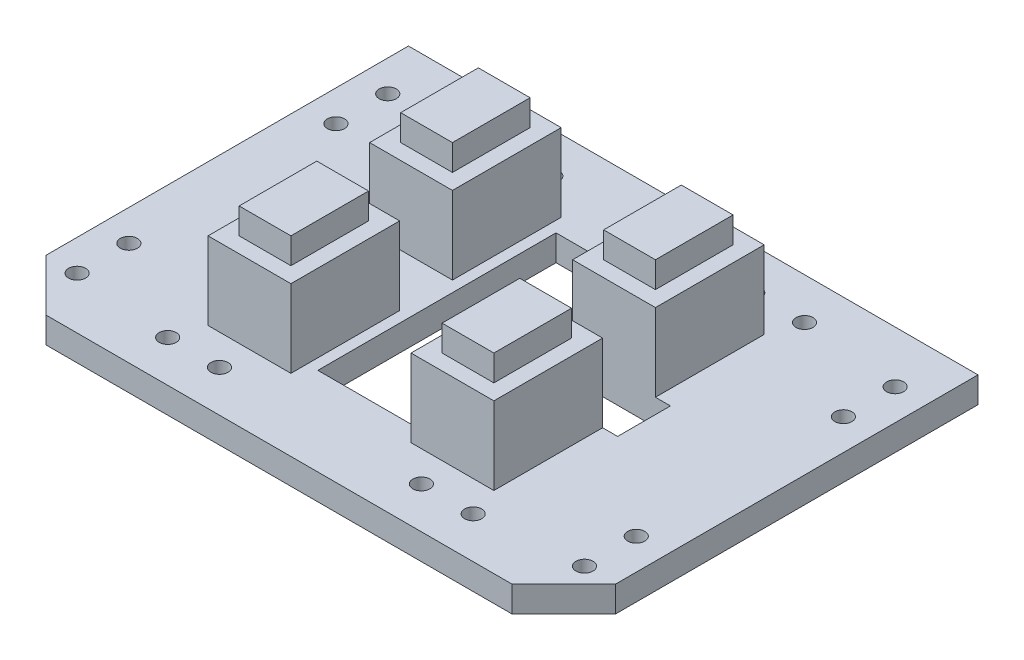
SolidWorks part; units mm, degrees
material "PLA+ esun"
ref_plane "Front Plane" through (0, 0, 0) normal (0, 0, 1) x (1, 0, 0)
ref_plane "Top Plane" through (0, 0, 0) normal (0, 1, 0) x (1, 0, 0)
ref_plane "Right Plane" through (0, 0, 0) normal (1, 0, 0) x (0, 0, -1)
sketch "Sketch1" plane through (0, 0, 0) normal (0, 1, 0) x (1, 0, 0)
  line L0 (0, 0) -> (49.8029, 0) construction
  line L1 (-77.5, 77.5) -> (77.5, 77.5)
  line L2 (-77.5, 77.5) -> (-77.5, -77.5)
  line L3 (-77.5, -77.5) -> (77.5, -77.5)
  line L4 (77.5, 77.5) -> (77.5, -77.5)
  line L5 (-77.5, 77.5) -> (77.5, -77.5) construction
  line L6 (-77.5, -77.5) -> (77.5, 77.5) construction
  line L7 (-9.5, 23) -> (9.5, 23)
  line L8 (-9.5, 23) -> (-9.5, -23)
  line L9 (-9.5, -23) -> (9.5, -23)
  line L10 (9.5, 23) -> (9.5, -23)
  line L11 (-9.5, 23) -> (9.5, -23) construction
  line L12 (-9.5, -23) -> (9.5, 23) construction
  line L14 (0, 0) -> (0, 35.7746) construction
  line L17 (-77.5, -77.5) -> (-42.5, -77.5)
  line L18 (-77.5, -77.5) -> (-77.5, -24.25)
  line L19 (-77.5, -24.25) -> (-42.5, -24.25)
  line L20 (-42.5, -77.5) -> (-42.5, -24.25)
  line L21 (-77.5, 24.25) -> (-42.5, 24.25)
  line L22 (-42.5, 77.5) -> (-42.5, 24.25)
  line L23 (42.5, -77.5) -> (42.5, -24.25)
  line L24 (77.5, -24.25) -> (42.5, -24.25)
  line L25 (42.5, 77.5) -> (42.5, 24.25)
  line L26 (77.5, 24.25) -> (42.5, 24.25)
  line L27 (20, -40) -> (42.5, -40)
  line L28 (-42.5, 24.25) -> (-77.5, 24.25)
  line L29 (-42.5, 24.25) -> (-42.5, -24.25)
  line L30 (-42.5, -24.25) -> (-77.5, -24.25)
  line L31 (-77.5, 24.25) -> (-77.5, -24.25)
  line L32 (42.5, 24.25) -> (77.5, 24.25)
  line L33 (42.5, 24.25) -> (42.5, -24.25)
  line L34 (42.5, -24.25) -> (77.5, -24.25)
  line L35 (77.5, 24.25) -> (77.5, -24.25)
  line L36 (-42.5, 77.5) -> (42.5, 77.5)
  line L37 (-42.5, 77.5) -> (-42.5, 40)
  line L38 (-42.5, 40) -> (42.5, 40)
  line L39 (42.5, 77.5) -> (42.5, 40)
  line L40 (-42.5, -77.5) -> (42.5, -77.5)
  line L41 (-42.5, -77.5) -> (-42.5, -40)
  line L42 (-42.5, -40) -> (-20, -40)
  line L43 (42.5, -77.5) -> (42.5, -40)
  line L45 (-20, -40) -> (-20, -77.5)
  line L46 (-20, -77.5) -> (20, -77.5)
  line L47 (20, -40) -> (20, -77.5)
  line L49 (-20, -77.5) -> (20, -77.5)
  line L50 (-20, -77.5) -> (-20, -40)
  line L51 (-20, -40) -> (20, -40)
  line L52 (20, -77.5) -> (20, -40)
  circle A1 centre (29.5, 32) radius 1.65
  circle A2 centre (19.5, 32) radius 1.65
  circle A3 centre (19.5, -32) radius 1.65
  circle A4 centre (29.5, -32) radius 1.65
  circle A5 centre (-29.5, -32) radius 1.65
  circle A6 centre (-19.5, -32) radius 1.65
  circle A7 centre (-19.5, 32) radius 1.65
  circle A8 centre (-29.5, 32) radius 1.65
  point P0 (0, 0)
  point P6 (0, 0)
  point P13 (0, 0)
  dimension "D5" = 9
  dimension "D8" = 20
  dimension "D9" = 53.25
  dimension "D6" = 3.3
  dimension "D1" = 155
  dimension "D2" = 155
  dimension "D3" = 46
  dimension "D4" = 19
  dimension "D7" = 2
  dimension "D10" = 35
  dimension "D11" = 37.5
  dimension "D12" = 37.5
  dimension "D13" = 22.5
  dimension "D14" = 22.5
extrude "Boss-Extrude3" add sketch "Sketch1" along normal blind 5 contours L4 L26 L25 L1 L22 L21 L2 L19 L20 L3 L23 L24 A7 A6 A5 A3 A2 A1 L7 L10 L9 L8 A4 A8 region at (0, 0, -38.8327)
sketch "Sketch6" plane through (0, 5, 0) normal (0, 1, 0) x (1, 0, 0)
  line L0 (-24.6, 8.1) -> (-14.6, 8.1)
  line L9 (-14.6, 8.1) -> (-14.6, 23.1)
  line L10 (-24.6, 8.1) -> (-24.6, 23.1)
  line L11 (-24.7, 8) -> (-14.5, 8)
  line L12 (-24.7, 23.2) -> (-14.5, 23.2)
  line L13 (-24.7, 23.2) -> (-24.7, -23.2)
  line L14 (-24.7, -23.2) -> (-14.5, -23.2)
  line L15 (-14.5, 23.2) -> (-14.5, -23.2)
  line L16 (9.5, 23) -> (-9.5, 23)
  line L17 (9.5, 23) -> (9.5, -23)
  line L18 (9.5, -23) -> (-9.5, -23)
  line L19 (-9.5, 23) -> (-9.5, -23)
  line L20 (9.5, 23) -> (-9.5, -23) construction
  line L21 (9.5, -23) -> (-9.5, 23) construction
  line L22 (-24.7, -8) -> (-14.5, -8)
  line L23 (0, 0) -> (0, -14.0514) construction
  line L24 (24.6, 23.1) -> (14.6, 23.1)
  line L29 (14.6, -8.1) -> (14.6, -23.1)
  line L30 (0, 0) -> (7.1407, 0) construction
  line L35 (-24.6, -8.1) -> (-14.6, -8.1)
  line L36 (-24.6, -8.1) -> (-24.6, -23.1)
  line L37 (-24.6, -23.1) -> (-14.6, -23.1)
  line L38 (-14.6, -8.1) -> (-14.6, -23.1)
  line L39 (-24.6, 23.1) -> (-14.6, 23.1)
  line L40 (24.6, -23.1) -> (14.6, -23.1)
  line L41 (24.6, -8.1) -> (24.6, -23.1)
  line L42 (24.6, -8.1) -> (14.6, -8.1)
  line L43 (24.7, -8) -> (14.5, -8)
  line L44 (14.5, 23.2) -> (14.5, -23.2)
  line L45 (24.7, -23.2) -> (14.5, -23.2)
  line L46 (24.7, 23.2) -> (24.7, -23.2)
  line L47 (24.7, 23.2) -> (14.5, 23.2)
  line L48 (24.7, 8) -> (14.5, 8)
  line L49 (24.6, 8.1) -> (24.6, 23.1)
  line L50 (14.6, 8.1) -> (14.6, 23.1)
  line L51 (24.6, 8.1) -> (14.6, 8.1)
  point P4 (0, 0)
  dimension "D1" = 0.2
  dimension "D2" = 5
  dimension "D3" = 0.2
  dimension "D4" = 10.2
  dimension "D5" = 15.2
  dimension "D6" = 15.2
  dimension "D7" = 0.1
  dimension "D8" = 0.1
  dimension "D9" = 0.1
  dimension "D10" = 0.1
extrude "Boss-Extrude4" add sketch "Sketch6" along normal blind 20 contours L51 L49 L24 L50 | L39 L10 L0 L9 | L38 L35 L36 L37 | L41 L42 L29 L40 region at (-19.6, 5, -15.6) region at (19.6, 5, -15.6) region at (19.6, 5, 15.6) region at (-19.6, 5, 15.6)
sketch "Sketch8" plane through (0, 5, 0) normal (0, 1, 0) x (1, 0, 0)
  line L0 (0, 0) -> (0, -16.476) construction
  line L1 (-27.6, 26.1) -> (-11.6, 26.1)
  line L2 (-27.6, 26.1) -> (-27.6, -26.1)
  line L3 (-27.6, -26.1) -> (-11.6, -26.1)
  line L4 (-11.6, 26.1) -> (-11.6, -26.1)
  line L5 (-24.6, 23.1) -> (-14.6, 23.1) construction
  line L6 (-24.6, 8.1) -> (-24.6, 23.1) construction
  line L7 (-14.6, 8.1) -> (-14.6, 23.1) construction
  line L8 (-24.6, -23.1) -> (-14.6, -23.1) construction
  line L9 (11.6, 26.1) -> (11.6, -26.1)
  line L10 (27.6, -26.1) -> (11.6, -26.1)
  line L11 (27.6, 26.1) -> (27.6, -26.1)
  line L12 (27.6, 26.1) -> (11.6, 26.1)
  line L13 (-24.6, 8.1) -> (-14.6, 8.1) construction
  line L14 (-27.6, 5.1) -> (-11.6, 5.1)
  line L15 (-27.6, 5.1) -> (-27.6, -5.1)
  line L16 (-27.6, -5.1) -> (-11.6, -5.1)
  line L17 (-11.6, 5.1) -> (-11.6, -5.1)
  line L18 (-24.6, -8.1) -> (-14.6, -8.1) construction
  line L19 (27.6, -5.1) -> (11.6, -5.1)
  line L20 (27.6, 5.1) -> (11.6, 5.1)
  line M8 (24.6, -8.1) -> (24.6, -23.1)
  line M9 (24.6, -23.1) -> (14.6, -23.1)
  line M10 (14.6, -23.1) -> (14.6, -8.1)
  line M11 (14.6, -8.1) -> (24.6, -8.1)
  line M12 (-14.6, -8.1) -> (-14.6, -23.1)
  line M13 (-14.6, -23.1) -> (-24.6, -23.1)
  line M14 (-24.6, -23.1) -> (-24.6, -8.1)
  line M15 (-24.6, -8.1) -> (-14.6, -8.1)
  line M16 (-24.6, 23.1) -> (-14.6, 23.1)
  line M17 (-14.6, 23.1) -> (-14.6, 8.1)
  line M18 (-14.6, 8.1) -> (-24.6, 8.1)
  line M19 (-24.6, 8.1) -> (-24.6, 23.1)
  line M20 (24.6, 8.1) -> (14.6, 8.1)
  line M21 (14.6, 8.1) -> (14.6, 23.1)
  line M22 (14.6, 23.1) -> (24.6, 23.1)
  line M23 (24.6, 23.1) -> (24.6, 8.1)
  dimension "D1" = 3
  dimension "D2" = 3
  dimension "D3" = 3
  dimension "D4" = 3
  dimension "D5" = 3
  dimension "D6" = 3
extrude "Boss-Extrude5" add sketch "Sketch8" along normal blind 15 contours L2 L14 L4 L1 M19 M16 M17 M18 | L16 L2 L3 L4 M15 M12 M13 M14 | L11 L19 L9 L10 M11 M8 M9 M10 | L20 L11 L12 L9 M23 M20 M21 M22 region at (-19.6, 5, -25.836) region at (-19.6, 5, 5.364) region at (19.6, 5, -25.836) region at (19.6, 5, 5.364)
sketch "Sketch5" plane through (0, 0, 0) normal (0, -1, 0) x (1, 0, 0)
  line L0 (9.5, -23) -> (9.5, 23) construction
  line L1 (14.5, 5.1) -> (30.5, 5.1)
  line L2 (14.5, 5.1) -> (14.5, -5.1)
  line L3 (14.5, -5.1) -> (30.5, -5.1)
  line L4 (30.5, 5.1) -> (30.5, -5.1)
  line L5 (-9.5, -23) -> (9.5, -23) construction
  line L6 (-9.5, 23) -> (9.5, 23) construction
  dimension "D1" = 5
  dimension "D2" = 16
  dimension "D3" = 17.9
  dimension "D4" = 17.9
extrude "Cut-Extrude1" cut sketch "Sketch5" against normal through all
sketch "Sketch10" plane through (0, 5, 0) normal (0, 1, 0) x (1, 0, 0)
  line L0 (-42.5, 40) -> (-42.5, -40) construction
  line L1 (-55, 40) -> (55, 40)
  line L2 (-55, 40) -> (-55, -40)
  line L3 (-55, -40) -> (55, -40)
  line L4 (55, 40) -> (55, -40)
  line L5 (-55, 40) -> (55, -40) construction
  line L6 (-55, -40) -> (55, 40) construction
  line L8 (0, 0) -> (13.414, 0) construction
  line L9 (13.414, 0) -> (0, 0) construction
  line L10 (0, 0) -> (0, -13.7533) construction
  line L11 (-55, 40) -> (-42.5, 40)
  line L12 (-55, 40) -> (-55, -40)
  line L13 (-55, -40) -> (-42.5, -40)
  line L14 (-42.5, 40) -> (-42.5, -40)
  line L15 (42.5, -40) -> (55, -40)
  line L16 (42.5, -40) -> (42.5, 40)
  line L17 (42.5, 40) -> (55, 40)
  line L18 (55, -40) -> (55, 40)
  circle A0 centre (-49, 30) radius 1.65
  circle A2 centre (-49, 20) radius 1.65
  circle A3 centre (49, 20) radius 1.65
  circle A4 centre (49, 30) radius 1.65
  circle A5 centre (49, -30) radius 1.65
  circle A6 centre (49, -20) radius 1.65
  circle A7 centre (-49, -20) radius 1.65
  circle A8 centre (-49, -30) radius 1.65
  point P0 (0, 0)
  line M21 (42.5, -40) -> (42.5, 40)
  line M23 (-42.5, 40) -> (-42.5, -40)
  dimension "D2" = 3.3
  dimension "D4" = 6
  dimension "D1" = 12.5
  dimension "D3" = 10
  dimension "D6" = 80
  dimension "D5" = 2
extrude "Boss-Extrude6" add sketch "Sketch10" against normal blind 5 contours L2 L3 L1 A7 A2 A0 A8 M23 | L4 L1 L3 A6 A5 A3 A4 M21 region at (-48.7411, 5, 0) region at (48.7411, 5, 0)
chamfer "Chamfer1" distance 10 angle 45 2 edges at (55, 2.5, 40) (-55, 2.5, 40)
